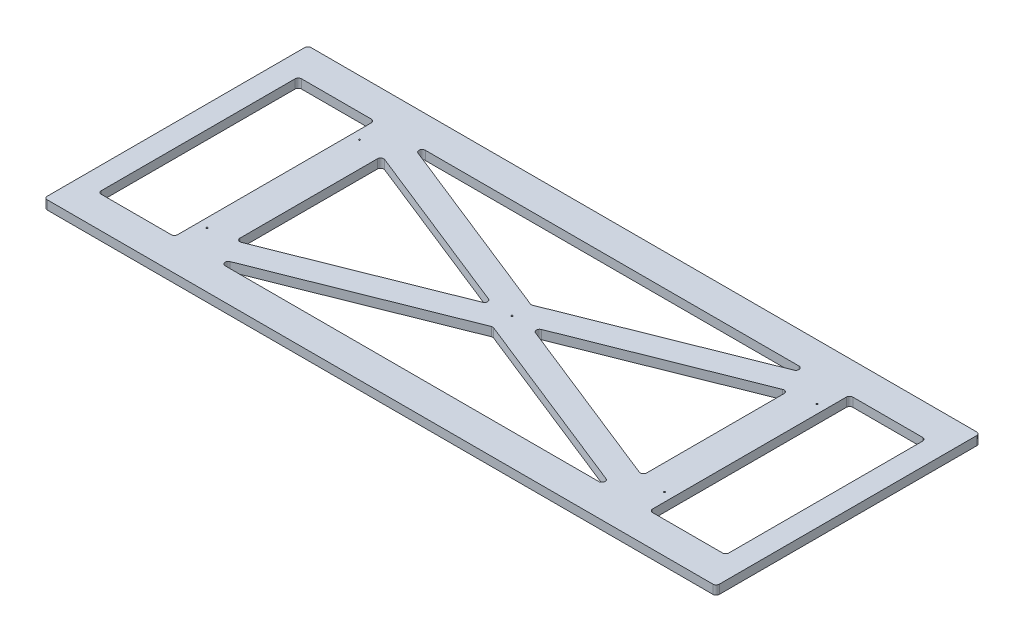
SolidWorks part; units mm, degrees
ref_plane "Front Plane" through (0, 0, 0) normal (0, 0, 1) x (1, 0, 0)
ref_plane "Top Plane" through (0, 0, 0) normal (0, 1, 0) x (1, 0, 0)
ref_plane "Right Plane" through (0, 0, 0) normal (1, 0, 0) x (0, 0, -1)
sketch "Sketch1" plane through (0, 0, 0) normal (0, 1, 0) x (1, 0, 0)
  line L1 (-671.5125, 263.525) -> (671.5125, 263.525)
  line L2 (-671.5125, 263.525) -> (-671.5125, -263.525)
  line L3 (-671.5125, -263.525) -> (671.5125, -263.525)
  line L4 (671.5125, 263.525) -> (671.5125, -263.525)
  line L5 (-671.5125, 263.525) -> (671.5125, -263.525) construction
  line L6 (-671.5125, -263.525) -> (671.5125, 263.525) construction
  point P0 (0, 0)
  dimension "D1" = 527.05
  dimension "D2" = 1343.025
extrude "Boss-Extrude1" add sketch "Sketch1" along normal blind 17.78
fillet "Fillet1" radius 6.35 4 edges at (-671.5125, 8.89, 263.525) (-671.5125, 8.89, -263.525) (671.5125, 8.89, -263.525) (671.5125, 8.89, 263.525)
hole_wizard "1/8 (0.125) Diameter Hole1" positions "Sketch3" profile "Sketch4" hole size "1/8" standard "ANSI Inch" end condition through all
sketch "Sketch3" plane through (0, 17.78, 0) normal (0, 1, 0) x (1, 0, 0)
  line L1 (-457.2, -152.4) -> (457.2, -152.4) construction
  line L2 (-457.2, -152.4) -> (-457.2, 152.4) construction
  line L3 (-457.2, 152.4) -> (457.2, 152.4) construction
  line L4 (457.2, -152.4) -> (457.2, 152.4) construction
  line L5 (-457.2, -152.4) -> (457.2, 152.4) construction
  line L6 (-457.2, 152.4) -> (457.2, -152.4) construction
  point P0 (0, 0)
  point P1 (457.2, 152.4)
  point P32 (-457.2, -152.4)
  point P33 (-457.2, 152.4)
  point P34 (457.2, -152.4)
  dimension "D1" = 914.4
  dimension "D2" = 304.8
sketch "Sketch4" plane through (0, 17.78, 0) normal (1, 0, 0) x (0, 0, 1)
  line L0 (0, 0) -> (0, 17.78)
  line L1 (0, 17.78) -> (1.5875, 17.78)
  line L2 (1.5875, 17.78) -> (1.5875, 0)
  line L5 (1.5875, 0) -> (0, 0)
  line L11 (0, -6.35) -> (0, 107.95) construction
  dimension "Thru Hole Dia." = 3.175
  dimension "Thru Hole Depth" = 17.78
sketch "Sketch2" plane through (0, 17.78, 0) normal (0, 1, 0) x (1, 0, 0)
  line L1 (-635, -330.2) -> (635, -330.2)
  line L2 (-635, -330.2) -> (-635, 330.2)
  line L3 (-635, 330.2) -> (635, 330.2)
  line L4 (635, -330.2) -> (635, 330.2)
  line L5 (-635, -330.2) -> (635, 330.2) construction
  line L6 (-635, 330.2) -> (635, -330.2) construction
  point P0 (0, 0)
  dimension "D1" = 660.4
  dimension "D2" = 1270
extrude "Boss-Extrude2" [suppressed] add sketch "Sketch2" along normal blind 9.525
sketch "Sketch5" plane through (0, 17.78, 0) normal (0, 1, 0) x (1, 0, 0)
  line L0 (-406.4, 200.025) -> (406.4, 200.025)
  line L1 (665.1625, 263.525) -> (-665.1625, 263.525) construction
  line L2 (0, 38.1) -> (-406.4, 200.025)
  line L3 (406.4, 200.025) -> (0, 38.1)
  line L4 (0, 263.525) -> (0, -263.525) construction
  line L5 (-665.1625, -263.525) -> (665.1625, -263.525) construction
  line L6 (-671.5125, 0) -> (671.5125, 0) construction
  line L7 (-671.5125, 257.175) -> (-671.5125, -257.175) construction
  line L8 (671.5125, -257.175) -> (671.5125, 257.175) construction
  line L9 (0, -38.1) -> (-406.4, -200.025)
  line L10 (-406.4, -200.025) -> (406.4, -200.025)
  line L11 (406.4, -200.025) -> (0, -38.1)
  line L12 (406.4, 146.7445) -> (406.4, -146.7445)
  line L13 (406.4, -146.7445) -> (38.1, 0)
  line L14 (406.4, 146.7445) -> (38.1, 0)
  line L15 (-406.4, 146.7445) -> (-38.1, 0)
  line L16 (-406.4, 146.7445) -> (-406.4, -146.7445)
  line L17 (-406.4, -146.7445) -> (-38.1, 0)
  line L18 (627.0625, -200.025) -> (474.6625, -200.025)
  line L19 (-627.0625, -200.025) -> (-474.6625, -200.025)
  line L20 (-627.0625, -200.025) -> (-627.0625, 200.025)
  line L21 (-627.0625, 200.025) -> (-474.6625, 200.025)
  line L22 (-474.6625, -200.025) -> (-474.6625, 200.025)
  line L23 (-627.0625, -200.025) -> (-474.6625, 200.025) construction
  line L24 (-627.0625, 200.025) -> (-474.6625, -200.025) construction
  line L25 (627.0625, -200.025) -> (627.0625, 200.025)
  line L26 (627.0625, 200.025) -> (474.6625, 200.025)
  line L27 (474.6625, -200.025) -> (474.6625, 200.025)
  circle A0 centre (0, 0) radius 38.1 construction
  point P3 (0, 200.025)
  point P30 (-550.8625, 0)
  dimension "D2" = 76.2
  dimension "D4" = 152.4
  dimension "D1" = 63.5
  dimension "D3" = 812.8
  dimension "D5" = 44.45
extrude "Cut-Extrude1" cut sketch "Sketch5" against normal through all
fillet "Fillet2" radius 6.35 20 edges at (474.6625, 8.89, -200.025) (474.6625, 8.89, 200.025) (627.0625, 8.89, 200.025) (406.4, 8.89, 146.7445) (406.4, 8.89, 200.025) (627.0625, 8.89, -200.025) (406.4, 8.89, -146.7445) (406.4, 8.89, -200.025) (38.1, 8.89, 0) (0, 8.89, 38.1) (0, 8.89, -38.1) (-38.1, 8.89, 0) (-406.4, 8.89, 200.025) (-406.4, 8.89, -200.025) (-406.4, 8.89, -146.7445) (-406.4, 8.89, 146.7445) (-627.0625, 8.89, 200.025) (-474.6625, 8.89, 200.025) (-474.6625, 8.89, -200.025) (-627.0625, 8.89, -200.025)
